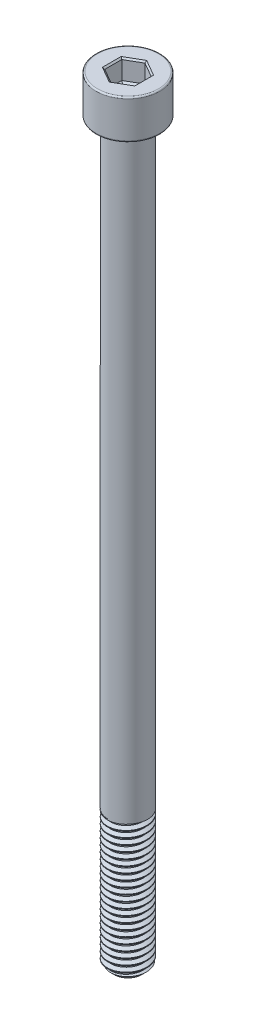
SolidWorks part; units mm, degrees
material "AISI Type A2 Tool Steel"
ref_plane "Front Plane" through (0, 0, 0) normal (0, 0, 1) x (1, 0, 0)
ref_plane "Top Plane" through (0, 0, 0) normal (0, 1, 0) x (1, 0, 0)
ref_plane "Right Plane" through (0, 0, 0) normal (1, 0, 0) x (0, 0, -1)
sketch "Sketch1" plane through (0, 0, 0) normal (0, 1, 0) x (1, 0, 0)
  circle A0 centre (0, 0) radius 4
  dimension "D1" = 8
extrude "Boss-Extrude1" add sketch "Sketch1" along normal blind 28
thread "Thread1" pitch 1.25 method cut profile "Thread Profile1" start angle 0, offset 2, length 0, pitch 1.25, diameter 8
ref_plane "Plane1" through (-4, 30, 0) normal (0, 0, 1) x (-1, 0, 0)
sketch "Thread Profile1" plane through (-4, 30, 0) normal (0, 0, 1) x (-1, 0, 0)
  line L0 (0, 0) -> (0, 1.25) construction
  line L11 (0, 0) -> (0, 1.0937)
  line L12 (0, 1.0937) -> (-0.6766, 0.7031)
  line L13 (-0.6766, 0.7031) -> (-0.6766, 0.3906)
  line L15 (-0.6766, 0.3906) -> (0, 0)
  line L17 (-0.6766, 0.5469) -> (0, 0.5469) construction
  point P2 (0, 0)
  dimension "Pitch" = 1.25
  dimension "Profile_Angle" = 60
  dimension "Profile_Land" = 0.3125
  dimension "Profile_Height" = 0.6766
sketch "Sketch2" plane through (0, 28, 0) normal (0, 1, 0) x (1, 0, 0)
  circle A0 centre (0, 0) radius 4
  dimension "D1" = 8
extrude "Boss-Extrude2" add sketch "Sketch2" along normal blind 122
sketch "Sketch5" plane through (0, 150, 0) normal (0, 1, 0) x (1, 0, 0)
  circle A0 centre (0, 0) radius 6.5
  dimension "D1" = 13
extrude "Boss-Extrude3" add sketch "Sketch5" along normal blind 8
sketch "Sketch6" plane through (0, 0, 0) normal (0, 0, 1) x (1, 0, 0)
  line L0 (0, 0) -> (0, 0.7245) construction
  line L1 (0, 0) -> (4.01, 0) construction
  line L2 (4.01, 0) -> (4.01, 1.2)
  line L3 (4.01, 1.2) -> (2.81, 0)
  line L4 (2.81, 0) -> (4.01, 0)
  dimension "D1" = 1.2
  dimension "D2" = 45
  dimension "D3" = 4.01
revolve "Cut-Revolve1" cut sketch "Sketch6" angle 360 about L0
fillet "Fillet1" radius 0.3 2 edges at (0, 150, 6.5) (0, 158, 6.5)
sketch "Sketch7" plane through (0, 158, 0) normal (0, 1, 0) x (1, 0, 0)
  line L1 (0, 3.4641) -> (-3, 1.7321)
  line L2 (-3, 1.7321) -> (-3, -1.7321)
  line L3 (-3, -1.7321) -> (0, -3.4641)
  line L4 (0, -3.4641) -> (3, -1.7321)
  line L5 (3, -1.7321) -> (3, 1.7321)
  line L6 (3, 1.7321) -> (0, 3.4641)
  circle A0 centre (0, 0) radius 3 construction
  dimension "D1" = 6
extrude "Cut-Extrude1" cut sketch "Sketch7" against normal blind 4
chamfer "Chamfer1" distance 0.3 angle 45 6 edges at (-3, 158, 0) (-1.5, 158, 2.5981) (1.5, 158, 2.5981) (3, 158, 0) (1.5, 158, -2.5981) (-1.5, 158, -2.5981)
sketch "Sketch8" plane through (0, 154, 0) normal (0, 1, 0) x (1, 0, 0)
  line L1 (0, 3.4641) -> (-3, 1.7321)
  line L2 (-3, 1.7321) -> (-3, -1.7321)
  line L3 (-3, -1.7321) -> (0, -3.4641)
  line L4 (0, -3.4641) -> (3, -1.7321)
  line L5 (3, -1.7321) -> (3, 1.7321)
  line L6 (3, 1.7321) -> (0, 3.4641)
  circle A0 centre (0, 0) radius 3 construction
extrude "Cut-Extrude2" cut sketch "Sketch8" against normal blind 0.4 draft 60
